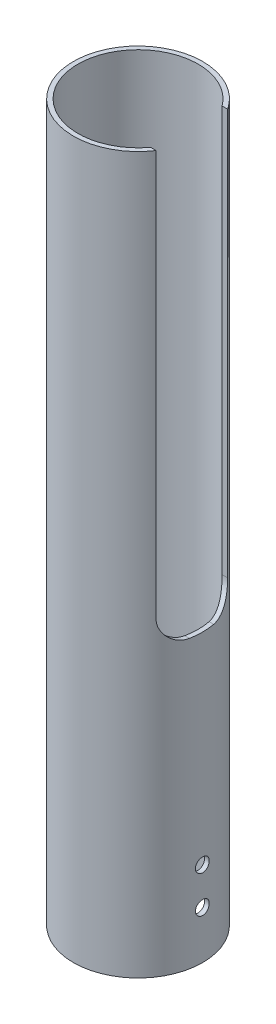
SolidWorks part; units mm, degrees
ref_plane "Front Plane" through (0, 0, 0) normal (0, 0, 1) x (1, 0, 0)
ref_plane "Top Plane" through (0, 0, 0) normal (0, 1, 0) x (1, 0, 0)
ref_plane "Right Plane" through (0, 0, 0) normal (1, 0, 0) x (0, 0, -1)
sketch "Sketch1" plane through (0, 0, 0) normal (0, 1, 0) x (1, 0, 0)
  circle A0 centre (0, 0) radius 27.1
  circle A1 centre (0, 0) radius 25.2
  dimension "D1" = 54.2
  dimension "D2" = 50.4
extrude "Boss-Extrude1" add sketch "Sketch1" along normal blind 300
sketch "Sketch2" plane through (0, 0, 0) normal (1, 0, 0) x (0, 0, -1)
  line L0 (0, 0) -> (0, 20)
  line L1 (0, 20) -> (0, 35.5)
  circle A0 centre (0, 20) radius 2.9
  circle A1 centre (0, 35.5) radius 2.9
  dimension "D1" = 5.8
  dimension "D2" = 5.8
  dimension "D3" = 20
  dimension "D4" = 15.5
extrude "Cut-Extrude1" cut sketch "Sketch2" against normal through all both and the other way through all contours A1 | L1 A0 L0 | L0 A0 L1 region at (0, 20, 1.2308) region at (0, 37.4926, 1.9926) region at (0, 20, -1.2308)
sketch "Sketch3" plane through (0, 0, 0) normal (1, 0, 0) x (0, 0, -1)
  line L0 (0, 328.0494) -> (0, 288.0308) construction
  line L1 (-15, 300) -> (15, 300)
  line L2 (-15, 300) -> (-15, 129.9)
  line L3 (-5.1, 120) -> (5.1, 120)
  line L4 (15, 300) -> (15, 129.9)
  line L5 (-25.2, 300) -> (25.2, 300)
  line L6 (-27.1, 0) -> (27.1, 0) construction
  arc A0 (5.1, 120) -> (15, 129.9) centre (5.1, 129.9) ccw
  arc A1 (-15, 129.9) -> (-5.1, 120) centre (-5.1, 129.9) ccw
  point P5 (0, 300)
  point P11 (0, 300)
  point P16 (15, 120)
  dimension "D4" = 9.9
  dimension "D1" = 30
  dimension "D2" = 120
  dimension "D3" = 180
extrude "Cut-Extrude2" cut sketch "Sketch3" along normal through all contours L0 L1 L2 A1 L3 | L5 L0 L3 A0 L4 region at (0, 210.6892, 0)
equation "\"TubeOutsideDiameter\"= 52"
equation "\"D1@Sketch1\"=\"CardTubeOutsideDiameter\""
equation "\"TubeInnerDiameter\"= 47.8"
equation "\"ReleaseMechanisumHeight\"=100"
equation "\"WireDiameter\"=3.38983"
equation "\"servoHoleDiameter\"= 2.8"
equation "\"CordDiameter\"= 5"
equation "\"MountingBoldDiameter\"=2.8"
equation "\"TubeMountingBoltDiameter\"= 5"
equation "\"D2@Sketch1\"=\"CardTubeInsideDiameter\""
equation "\"CardTubeOutsideDiameter\"= 54.2"
equation "\"CardTubeInsideDiameter\"= 50.4"
equation "\"D1@Sketch2\"=\"TubeMountingBoltDiameter\"+0.8"
equation "\"D2@Sketch2\"=\"TubeMountingBoltDiameter\"+0.8"
